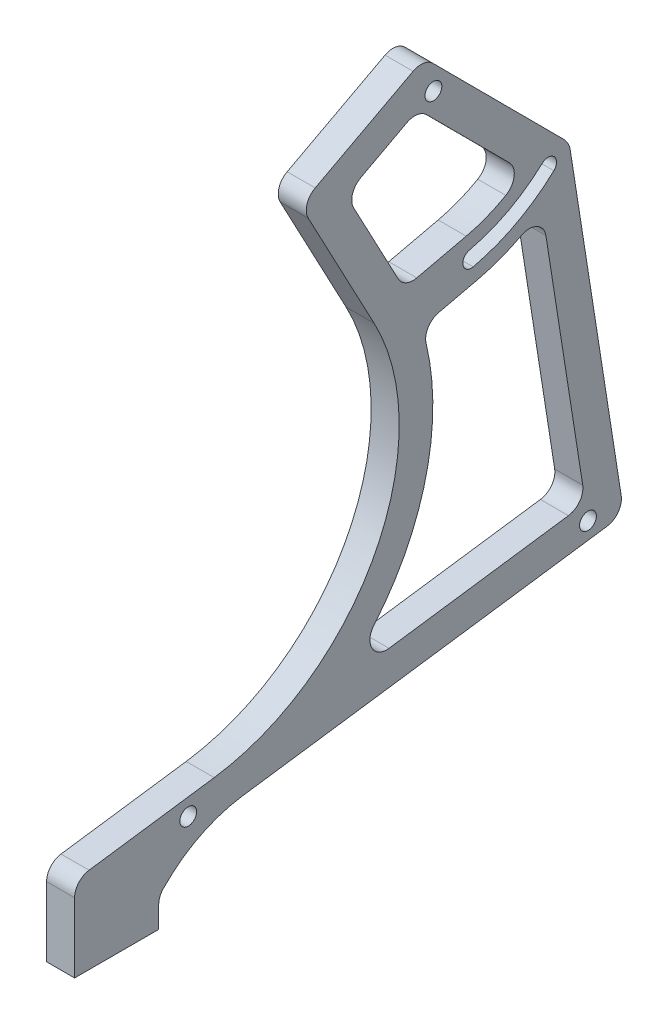
SolidWorks part; units mm, degrees
ref_plane "Front Plane" through (0, 0, 0) normal (0, 0, 1) x (1, 0, 0)
ref_plane "Top Plane" through (0, 0, 0) normal (0, 1, 0) x (1, 0, 0)
ref_plane "Right Plane" through (0, 0, 0) normal (1, 0, 0) x (0, 0, -1)
sketch "Sketch1" plane through (0, 0, 0) normal (1, 0, 0) x (0, 0, -1)
  line L0 (0, 0) -> (0, 15)
  line L1 (0, 15) -> (97.0463, 28.639) construction
  line L2 (97.0463, 28.639) -> (97.9763, 22.7107)
  line L3 (97.9763, 22.7107) -> (30, 13.1573)
  line L5 (15, 5) -> (15, 0)
  line L6 (15, 0) -> (0, 0)
  line L11 (70.7485, 75.7689) -> (64, 105) construction
  line L12 (64, 105) -> (84.46, 83.0594) construction
  line L13 (0, 15) -> (24.9025, 18.4998)
  line L14 (62.3411, 110.9134) -> (40.2674, 99.1766)
  line L15 (40.2674, 99.1766) -> (53.4126, 74.4541)
  line L17 (62.3411, 110.9134) -> (87.2928, 85.8834)
  line L18 (64, 105) -> (78.0841, 78.5116) construction
  line L19 (46.84, 86.8153) -> (78.3511, 103.5701) construction
  line L20 (88.4116, 83.6793) -> (97.0463, 28.639)
  line L21 (46.9564, 21.5993) -> (91.1039, 27.8038)
  line L22 (91.1039, 27.8038) -> (83.3764, 77.0616)
  line L23 (80.1087, 84.5914) -> (61.2314, 103.5279)
  line L24 (61.2314, 103.5279) -> (48.382, 96.6957)
  line L25 (48.382, 96.6957) -> (58.7937, 77.1141)
  line L26 (58.7937, 77.1141) -> (69.8487, 79.6664)
  line L27 (61.9004, 69.6209) -> (71.6483, 71.8714)
  arc A0 (15, 5) -> (30, 13.1573) centre (33.3867, -10.9404) cw
  circle A4 centre (64, 105) radius 1.5
  arc A5 (84.46, 83.0594) -> (70.7485, 75.7689) centre (64, 105) cw construction
  arc A6 (71.086, 74.3073) -> (85.4829, 81.9624) centre (64, 105) ccw
  arc A7 (70.4111, 77.2305) -> (83.437, 84.1564) centre (64, 105) ccw
  arc A8 (70.4111, 77.2305) -> (71.086, 74.3073) centre (70.7485, 75.7689) ccw
  arc A9 (85.4829, 81.9624) -> (83.437, 84.1564) centre (84.46, 83.0594) ccw
  arc A10 (71.6483, 71.8714) -> (83.3764, 77.0616) centre (64, 105) ccw
  arc A11 (53.4126, 74.4541) -> (24.9025, 18.4998) centre (19.5678, 56.4584) cw
  arc A12 (46.9564, 21.5993) -> (61.9004, 69.6209) centre (19.5678, 56.4584) ccw
  circle A13 centre (70.7485, 75.7689) radius 4 construction
  arc A15 (69.8487, 79.6664) -> (80.1087, 84.5914) centre (64, 105) ccw
  arc A17 (87.2928, 85.8834) -> (88.4116, 83.6793) centre (84.46, 83.0594) cw
  point P7 (0, 0)
  point P24 (78.0841, 78.5116)
  dimension "D8" = 105
  dimension "D9" = 98
  dimension "D11" = 3
  dimension "D12" = 30
  dimension "D14" = 64
  dimension "D21" = 6
  dimension "D23" = 25
  dimension "D24" = 6
  dimension "D25" = 1.5
  dimension "D26" = 8
  dimension "D32" = 4
  dimension "D33" = 8
  dimension "D18" = 4
  dimension "D1" = 6
  dimension "D4" = 15
  dimension "D5" = 5
  dimension "D6" = 15
  dimension "D7" = 30
  dimension "D15" = 62
  dimension "D16" = 30
  dimension "D17" = 6
  dimension "D19" = 28
  dimension "D20" = 3
  dimension "D27" = 12
  dimension "D28" = 6
  dimension "D29" = 6
  dimension "D31" = 6
extrude "Boss-Extrude1" add sketch "Sketch1" along normal blind 5
fillet "Fillet1" radius 3 13 edges at (2.5, 27.8038, -91.1039) (2.5, 21.5993, -46.9564) (2.5, 84.5914, -80.1087) (2.5, 110.9134, -62.3411) (2.5, 103.5279, -61.2314) (2.5, 96.6957, -48.382) (2.5, 77.1141, -58.7937) (2.5, 15, 0) (2.5, 69.6209, -61.9004) (2.5, 77.0616, -83.3764) (2.5, 99.1766, -40.2674) (2.5, 22.7107, -97.9763) (2.5, 5, -15)
hole_wizard "Tap Drill for M3 Tap1" positions "Sketch4" profile "Sketch3" hole size "M3" standard "ISO"
sketch "Sketch4" plane through (0, 0, 0) normal (0, -1, 0) x (-1, 0, 0)
  line L0 (0, 0) -> (0, 15) construction
  line L1 (-5, 0) -> (0, 0) construction
  point P0 (-2.5, 5.5)
  point P2 (-2.5, 70.5)
  dimension "D1" = 2.5
  dimension "D2" = 5.5
  dimension "D3" = 65
sketch "Sketch3" plane through (2.5, 0, -5.5) normal (1, 0, 0) x (0, 0, -1)
  line L0 (0, 0) -> (0, 7.7511)
  line L1 (0, 7.7511) -> (1.25, 7)
  line L2 (1.25, 7) -> (1.25, 0)
  line L5 (1.25, 0) -> (0, 0)
  line L10 (0, 7.7511) -> (-1.25, 7) construction
  line L11 (0, -6.35) -> (0, 107.95) construction
  dimension "Hole Dia." = 2.5
  dimension "Hole Depth" = 7
  dimension "Drill Angle" = 118
sketch "Sketch7" plane through (5, 0, 0) normal (1, 0, 0) x (0, 0, -1)
  line L0 (24.9025, 18.4998) -> (2.5825, 15.3629) construction
  line L3 (56.0914, 22.8831) -> (88.0852, 27.3796) construction
  line L4 (97.5038, 25.7222) -> (88.4116, 83.6793) construction
  circle A0 centre (20.2696, 14.8192) radius 1.5
  circle A1 centre (91.5689, 24.8397) radius 1.5
  dimension "D1" = 3
  dimension "D4" = 72
  dimension "D2" = 3
  dimension "D3" = 3
  dimension "D5" = 6
extrude "Cut-Extrude2" cut sketch "Sketch7" against normal up to next
equation "\"ˇ3\"=3.9176"
